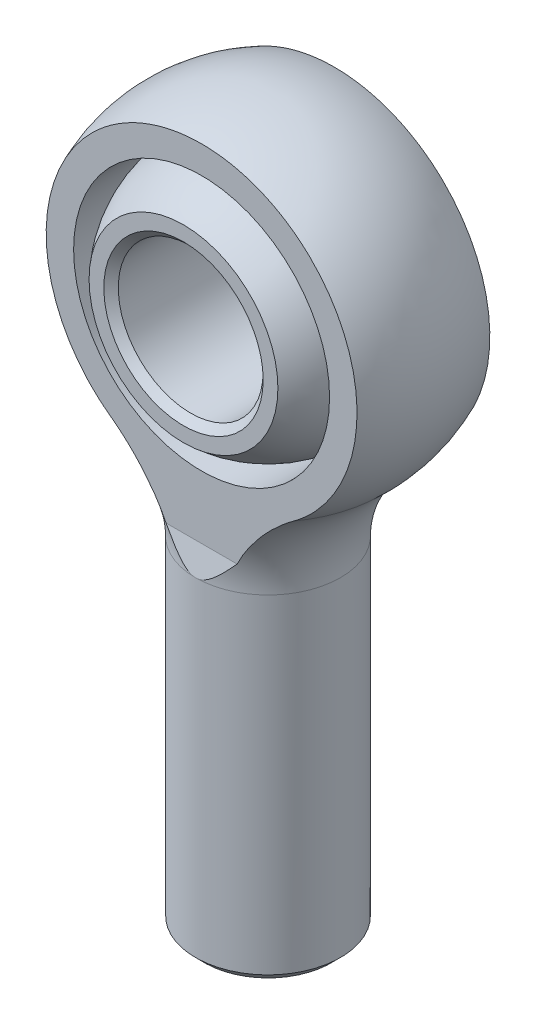
SolidWorks part; units mm, degrees
ref_plane "Front" through (0, 0, 0) normal (0, 0, 1) x (1, 0, 0)
ref_plane "Top" through (0, 0, 0) normal (0, 1, 0) x (1, 0, 0)
ref_plane "Right" through (0, 0, 0) normal (1, 0, 0) x (0, 0, -1)
sketch "Sketch1" plane through (0, 0, 0) normal (0, 0, 1) x (1, 0, 0)
  line L0 (0, 0) -> (0, -44.45)
  line L1 (0, -44.45) -> (9.525, -44.45)
  line L2 (9.525, -44.45) -> (9.525, 0)
  line L3 (9.525, 0) -> (0, 0)
  line L5 (0, 50.8) -> (0, 0) construction
  line L6 (0, 50.8) -> (22.225, 50.8) construction
  line L7 (22.225, 50.8) -> (22.225, 28.575) construction
  line L8 (-9.525, -44.45) -> (-9.525, 0) construction
  arc A0 (14.893, 12.0781) -> (0, 50.8) centre (0, 28.575) ccw construction
  circle A1 centre (0, 28.575) radius 9.525 construction
  circle A2 centre (0, 28.575) radius 16.6624 construction
  circle A3 centre (0, 28.575) radius 16.829 construction
  arc A4 (9.525, 0) -> (14.893, 12.0781) centre (25.7969, 0) cw construction
  point P16 (-9.525, -32.5438)
  dimension "A" = 19.05
  dimension "Ball Dia" = 33.3248
  dimension "B" = 44.45
  dimension "D1" = 33.658
  dimension "D" = 73.025
  dimension "E" = 44.45
  dimension "Thread Dia" = 19.05
  dimension "D2" = 11.9062
revolve "Revolve1" add sketch "Sketch1" angle 360 about L5 other way angle 360
sketch "Sketch13" plane through (0, -44.45, 0) normal (0, -1, 0) x (1, 0, 0)
  circle A0 centre (0, 0) radius 9.525 construction
  circle A1 centre (0, 0) radius 9.525
curve "Helix/Spiral1" [suppressed] pitch 1.5875 height 46.0375 turns 29 parameters "Pitch"=1.5875
chamfer "Chamfer2" distance 1.1906 angle 45 1 edges at (-9.525, -44.45, 0)
sketch "Sketch14" plane through (0, 0, 0) normal (0, 0, 1) x (1, 0, 0)
  line L0 (8.4939, -45.2437) -> (9.525, -45.8391)
  line L1 (9.525, -45.8391) -> (9.525, -44.45)
  line L2 (9.525, -44.45) -> (8.4939, -45.0453)
  line L3 (8.4939, -45.0453) -> (8.4939, -45.2437)
  line L4 (9.0094, -44.7477) -> (9.0094, -45.5414) construction
  dimension "D1" = 0.7937
  dimension "D3" = 60
  dimension "D2" = 0.1984
sweep "Cut-Sweep1" [suppressed] cut profiles "Sketch14" path "Helix/Spiral1"
sketch "Sketch4" plane through (0, 0, 0) normal (0, 0, 1) x (1, 0, 0)
  line L0 (9.525, 0) -> (0, 0) construction
  line L2 (0, 50.8) -> (0, 0) construction
  line L3 (9.525, 0) -> (0, 0)
  line L5 (0, 50.8) -> (0, 0)
  line L6 (0, 50.8) -> (0, 53.34) construction
  arc A0 (14.893, 12.0781) -> (0, 50.8) centre (0, 28.575) ccw construction
  arc A1 (14.893, 12.0781) -> (0, 50.8) centre (0, 28.575) ccw
  arc A2 (14.893, 12.0781) -> (9.525, 0) centre (25.7969, 0) ccw construction
  arc A3 (14.893, 12.0781) -> (9.525, 0) centre (25.7969, 0) ccw
  dimension "D1" = 2.54
revolve "Revolve2" add sketch "Sketch4" angle 360 about L6
sketch "Sketch5" plane through (0, 0, 0) normal (1, 0, 0) x (0, 0, -1)
  line L0 (8.7312, 50.8) -> (22.225, 50.8)
  line L1 (-8.7312, 50.8) -> (8.7312, 50.8) construction
  line L2 (-8.7312, 50.8) -> (-8.7312, 3.4925)
  line L3 (-9.525, 0) -> (9.525, 0) construction
  line L4 (8.7312, 50.8) -> (8.7312, 3.4925)
  line L5 (22.225, 50.8) -> (22.225, 0)
  line L6 (22.225, 0) -> (9.525, 0)
  line L7 (-9.525, 0) -> (-22.225, 0)
  line L8 (-22.225, 0) -> (-22.225, 50.8)
  line L9 (-22.225, 50.8) -> (-8.7312, 50.8)
  line L10 (9.525, 0) -> (8.7312, 3.4925)
  line L11 (-9.525, 0) -> (-8.7312, 3.4925)
  line L12 (-8.7312, 3.4925) -> (8.7312, 3.4925) construction
  line L13 (0, 0) -> (0, 3.4925) construction
  arc A0 (14.893, 12.0781) -> (-14.893, 12.0781) centre (0, 28.575) ccw construction
  dimension "F" = 17.4625
  dimension "D2" = 3.4925
  dimension "D1" = 19.05
extrude "Cut-Extrude1" cut sketch "Sketch5" against normal through all and the other way through all
sketch "Sketch6" plane through (0, 0, 0) normal (0, 0, 1) x (1, 0, 0)
  circle A0 centre (0, 28.575) radius 16.829 construction
  circle A1 centre (0, 28.575) radius 16.829
extrude "Cut-Extrude2" cut sketch "Sketch6" against normal through all and the other way through all
sketch "Sketch7" plane through (0, 0, 0) normal (0, 0, 1) x (1, 0, 0)
  line L0 (0, 45.2374) -> (0, 11.9126)
  line L1 (0, 50.8) -> (0, 0) construction
  line L2 (0, 0) -> (0, 11.9126) construction
  arc A0 (0, 11.9126) -> (0, 45.2374) centre (0, 28.575) ccw
  circle A1 centre (0, 28.575) radius 16.6624 construction
revolve "Revolve3" add sketch "Sketch7" angle 360 about L2
sketch "Sketch8" plane through (0, 0, 0) normal (1, 0, 0) x (0, 0, -1)
  line L0 (-8.7312, 50.8) -> (8.7312, 50.8) construction
  line L1 (-11.1125, 50.8) -> (11.1125, 50.8) construction
  line L2 (-11.1125, 50.8) -> (-11.1125, 0)
  line L3 (-11.1125, 0) -> (11.1125, 0) construction
  line L4 (11.1125, 50.8) -> (11.1125, 0)
  line L5 (11.1125, 50.8) -> (22.225, 50.8)
  line L6 (22.225, 50.8) -> (22.225, 0)
  line L7 (22.225, 0) -> (11.1125, 0)
  line L8 (-11.1125, 0) -> (-22.225, 0)
  line L9 (-22.225, 0) -> (-22.225, 50.8)
  line L10 (-22.225, 50.8) -> (-11.1125, 50.8)
  dimension "C" = 22.225
extrude "Cut-Extrude3" cut sketch "Sketch8" against normal through all and the other way through all
sketch "Sketch10" plane through (0, 0, 0) normal (0, 0, 1) x (1, 0, 0)
  circle A0 centre (0, 28.575) radius 9.525 construction
  circle A1 centre (0, 28.575) radius 9.525
extrude "Cut-Extrude4" cut sketch "Sketch10" against normal through all and the other way through all
chamfer "Chamfer1" distance 0.9525 angle 45 2 edges at (9.525, 28.575, -11.1125) (9.525, 28.575, 11.1125)
sketch "Sketch11" plane through (0, 0, 0) normal (1, 0, 0) x (0, 0, -1)
  line L0 (0, 28.575) -> (-11.1125, 29.9394) construction
  line L1 (8.7312, 28.575) -> (-8.7312, 28.575) construction
  line L2 (0, 28.575) -> (-11.1125, 27.2106) construction
  line L3 (0, 50.8) -> (0, 0) construction
  line L4 (-11.1125, 50.8) -> (-11.1125, 0) construction
  line L5 (0, 28.575) -> (0.0074, 28.575) construction
  dimension "Swivel" = 14
ref_axis "Centre Axis" through (0, 28.575, -10.16) along (0, 0, 1)
equation "\"D1@Sketch1\"=\"Ball Dia@Sketch1\"*1.01"
equation "\"D1@Chamfer1\"=\"A@Sketch1\"/20"
equation "\"D1@Sketch5\"=\"Thread Dia@Sketch1\""
equation "\"D2@Sketch5\"=\"F@Sketch5\"/5"
equation "\"D1@Sketch14\" = \"Pitch@Helix/Spiral1\" * .5"
equation "\"D2@Sketch14\" = \"Pitch@Helix/Spiral1\" * .125"
equation "\"D3@Helix/Spiral1\" = \"E@Sketch1\" + \"Pitch@Helix/Spiral1\""
equation "\"D1@Chamfer2\" = \"Pitch@Helix/Spiral1\" * .75"
equation "\"D2@Sketch1\" = \"Pitch@Helix/Spiral1\" * 7.5"
